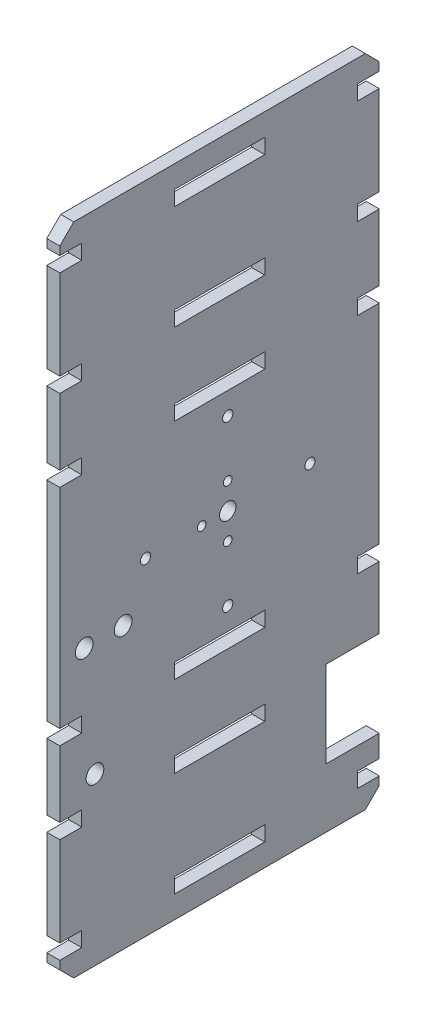
SolidWorks part; units mm, degrees
ref_plane "Front" through (0, 0, 0) normal (0, 0, 1) x (1, 0, 0)
ref_plane "Top" through (0, 0, 0) normal (0, 1, 0) x (1, 0, 0)
ref_plane "Right" through (0, 0, 0) normal (1, 0, 0) x (0, 0, -1)
ref_axis "side-side" through (80.9, 0, 0) along (-1, 0, 0)
ref_axis "up-down" through (0, 50, 0) along (0, -1, 0)
ref_axis "front-back" through (0, 0, -80.9) along (0, 0, 1)
sketch "Sketch1" plane through (0, 0, 0) normal (1, 0, 0) x (0, 0, -1)
  line L1 (-58.293, 119.489) -> (58.293, 119.489)
  line L2 (-58.293, 119.489) -> (-58.293, 111.361)
  line L3 (-58.293, -119.489) -> (58.293, -119.489)
  line L4 (58.293, 119.489) -> (58.293, 111.361)
  line L6 (0, 50) -> (0, -50) construction
  line L7 (-58.293, 111.361) -> (-50.293, 111.361) construction
  line L8 (58.293, -111.361) -> (50.293, -111.361) construction
  line L9 (58.415, -69.422) -> (41.905, -69.422) construction
  line L10 (58.293, -66.374) -> (38.857, -66.374)
  line L11 (58.293, -97.87) -> (58.293, -105.9)
  line L12 (58.293, -97.87) -> (38.857, -97.87)
  line L13 (38.857, -66.374) -> (38.857, -97.87)
  line L14 (55.24, -94.822) -> (41.905, -94.822) construction
  line L16 (0, -111.361) -> (83.6295, -111.361) construction
  line L17 (58.293, -105.9) -> (50.293, -105.9)
  line L18 (0, -43.561) -> (92, -43.561) construction
  line L19 (58.293, -111.361) -> (50.293, -111.361)
  line L20 (50.293, -105.9) -> (50.293, -111.361)
  line L21 (58.293, -111.361) -> (58.293, -119.489)
  line L22 (58.293, -43.561) -> (58.293, -66.374)
  line L23 (58.293, -38.1) -> (50.293, -38.1)
  line L24 (83.6295, 105.9) -> (0, 105.9) construction
  line L25 (58.293, -43.561) -> (50.293, -43.561)
  line L26 (50.293, -38.1) -> (50.293, -43.561)
  line L27 (83.6295, 67.8) -> (0, 67.8) construction
  line L28 (58.293, 111.361) -> (50.293, 111.361)
  line L29 (58.293, 67.8) -> (58.293, 43.561)
  line L30 (58.293, 105.9) -> (50.293, 105.9)
  line L31 (50.293, 111.361) -> (50.293, 105.9)
  line L32 (58.293, 38.1) -> (-58.293, 38.1) construction
  line L33 (58.293, 73.261) -> (50.293, 73.261)
  line L34 (58.293, 38.1) -> (58.293, -38.1)
  line L35 (58.293, 67.8) -> (50.293, 67.8)
  line L36 (50.293, 73.261) -> (50.293, 67.8)
  line L37 (0, 67.8) -> (-83.6295, 67.8) construction
  line L38 (58.293, 43.561) -> (50.293, 43.561)
  line L39 (-58.293, 105.9) -> (-58.293, 73.261)
  line L40 (58.293, 38.1) -> (50.293, 38.1)
  line L41 (50.293, 43.561) -> (50.293, 38.1)
  line L42 (0, 105.9) -> (-83.6295, 105.9) construction
  line L43 (-58.293, 43.561) -> (-50.293, 43.561)
  line L44 (-58.293, -43.561) -> (-58.293, -67.8)
  line L45 (-58.293, 38.1) -> (-50.293, 38.1)
  line L46 (-50.293, 43.561) -> (-50.293, 38.1)
  line L47 (-58.293, 73.261) -> (-50.293, 73.261)
  line L48 (-58.293, 38.1) -> (-58.293, -38.1)
  line L49 (-58.293, 67.8) -> (-50.293, 67.8)
  line L50 (-50.293, 73.261) -> (-50.293, 67.8)
  line L51 (83.6295, 111.361) -> (0, 111.361) construction
  line L52 (-58.293, 111.361) -> (-50.293, 111.361)
  line L53 (-58.293, 67.8) -> (-58.293, 43.561)
  line L54 (-58.293, 105.9) -> (-50.293, 105.9)
  line L55 (-50.293, 111.361) -> (-50.293, 105.9)
  line L56 (83.6295, 73.261) -> (0, 73.261) construction
  line L57 (16.51, 111.361) -> (-16.51, 111.361)
  line L58 (16.51, 111.361) -> (16.51, 105.9)
  line L59 (16.51, 105.9) -> (-16.51, 105.9)
  line L60 (-16.51, 111.361) -> (-16.51, 105.9)
  line L61 (92, 43.561) -> (0, 43.561) construction
  line L62 (16.51, 73.261) -> (-16.51, 73.261)
  line L63 (16.51, 73.261) -> (16.51, 67.8)
  line L64 (16.51, 67.8) -> (-16.51, 67.8)
  line L65 (-16.51, 73.261) -> (-16.51, 67.8)
  line L67 (16.51, 43.561) -> (-16.51, 43.561)
  line L68 (16.51, 43.561) -> (16.51, 38.1)
  line L69 (16.51, 38.1) -> (-16.51, 38.1)
  line L70 (-16.51, 43.561) -> (-16.51, 38.1)
  line L72 (-58.293, -38.1) -> (58.293, -38.1) construction
  line L73 (16.51, -38.1) -> (-16.51, -38.1)
  line L74 (16.51, -38.1) -> (16.51, -43.561)
  line L75 (16.51, -43.561) -> (-16.51, -43.561)
  line L77 (-16.51, -38.1) -> (-16.51, -43.561)
  line L78 (-92, -43.561) -> (0, -43.561) construction
  line L79 (0, -67.8) -> (83.6295, -67.8) construction
  line L80 (16.51, -67.8) -> (-16.51, -67.8)
  line L81 (16.51, -67.8) -> (16.51, -73.261)
  line L82 (16.51, -73.261) -> (-16.51, -73.261)
  line L83 (-16.51, -67.8) -> (-16.51, -73.261)
  line L84 (-83.6295, -73.261) -> (0, -73.261) construction
  line L85 (0, -105.9) -> (83.6295, -105.9) construction
  line L86 (16.51, -105.9) -> (-16.51, -105.9)
  line L87 (16.51, -105.9) -> (16.51, -111.361)
  line L88 (16.51, -111.361) -> (-16.51, -111.361)
  line L89 (-16.51, -105.9) -> (-16.51, -111.361)
  line L90 (-83.6295, -111.361) -> (0, -111.361) construction
  line L91 (0, 111.361) -> (0, 119.489) construction
  line L92 (58.293, 105.9) -> (58.293, 73.261)
  line L93 (-58.293, -38.1) -> (-50.293, -38.1)
  line L94 (-58.293, -73.261) -> (-58.293, -105.9)
  line L95 (-58.293, -43.561) -> (-50.293, -43.561)
  line L96 (-50.293, -38.1) -> (-50.293, -43.561)
  line L97 (-58.293, -67.8) -> (-50.293, -67.8)
  line L98 (-58.293, -111.361) -> (-58.293, -119.489)
  line L99 (-58.293, -73.261) -> (-50.293, -73.261)
  line L100 (-50.293, -67.8) -> (-50.293, -73.261)
  line L101 (-58.293, -105.9) -> (-50.293, -105.9)
  line L103 (-58.293, -111.361) -> (-50.293, -111.361)
  line L104 (-50.293, -105.9) -> (-50.293, -111.361)
  circle A0 centre (3, 9.5191) radius 1.5875
  circle A1 centre (-6.5191, 0) radius 1.5875
  circle A2 centre (3, -9.5191) radius 1.5875
  circle A3 centre (3, 0) radius 3
  circle A4 centre (-35.174, -17.15) radius 3.2385
  circle A5 centre (-49.398, -17.15) radius 3.2385
  circle A6 centre (-45.464, -58.873) radius 3.2385
  circle A7 centre (33, 0) radius 1.8669
  circle A8 centre (3, 30) radius 1.8669
  circle A9 centre (-27, 0) radius 1.8669
  circle A10 centre (3, -30) radius 1.8669
  point P8 (0, 119.489)
  point P118 (-16.51, 108.6305)
  dimension "D8" = 6.477
  dimension "D9" = 6
  dimension "D10" = 3.175
  dimension "D11" = 3.7338
  dimension "D1" = 33.02
  dimension "D2" = 8.128
  dimension "D3" = 8.128
  dimension "D4" = 3.048
  dimension "D5" = 3.048
  dimension "D6" = 3.048
  dimension "D7" = 8
extrude "Boss-Extrude1" add sketch "Sketch1" against normal blind 4.7625
chamfer "Chamfer1" distance 5.08 angle 45 4 edges at (-2.3813, 119.489, 58.293) (-2.3813, 119.489, -58.293) (-2.3813, -119.489, 58.293) (-2.3813, -119.489, -58.293)
